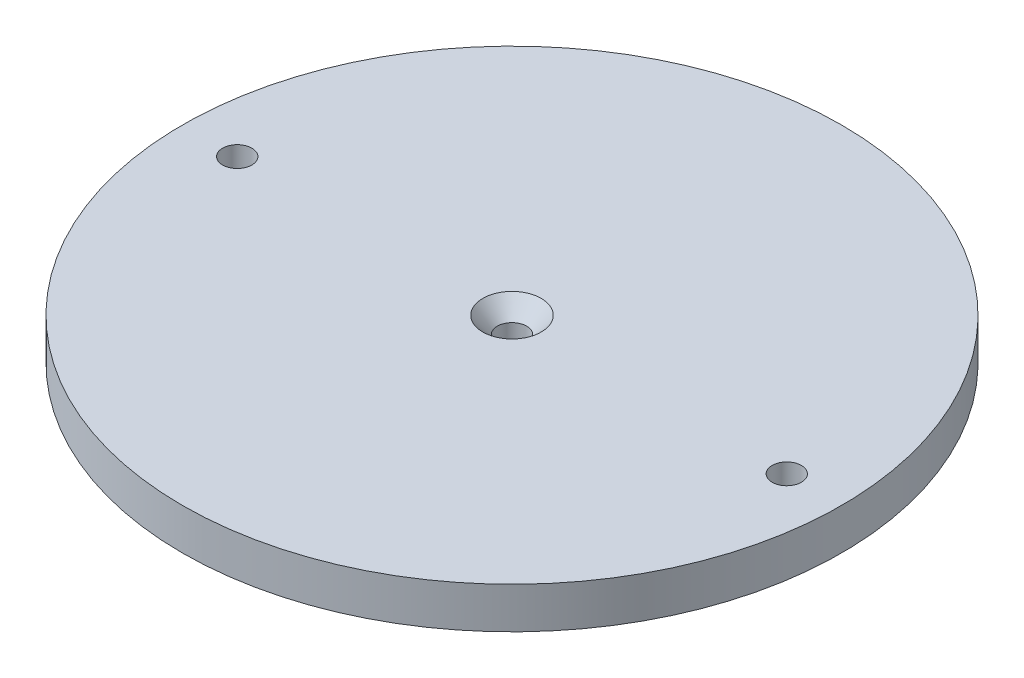
SolidWorks part; units mm, degrees
material "6061 Alloy"
ref_plane "Front Plane" through (0, 0, 0) normal (0, 0, 1) x (1, 0, 0)
ref_plane "Top Plane" through (0, 0, 0) normal (0, 1, 0) x (1, 0, 0)
ref_plane "Right Plane" through (0, 0, 0) normal (1, 0, 0) x (0, 0, -1)
sketch "Sketch2" plane through (0, 0, 0) normal (0, 1, 0) x (1, 0, 0)
  circle A0 centre (0, 0) radius 76.1619
  dimension "D1" = 152.3238
extrude "Boss-Extrude1" add sketch "Sketch2" along normal blind 9.525
sketch "Sketch3" plane through (0, 9.525, 0) normal (0, 1, 0) x (1, 0, 0)
  point P0 (-63.5, 0)
  point P1 (63.5, 0)
  point P2 (-63.2099, 6.0633)
  point P4 (0, 0)
  dimension "D1" = 63.5
  dimension "D2" = 63.5
hole_wizard "1/4 Clearance Hole1" positions "Sketch3" profile "Sketch4" hole size "1/4" standard "ANSI Inch" end condition through all
sketch "Sketch4" plane through (-63.5, 9.525, 0) normal (1, 0, 0) x (0, 0, 1)
  line L0 (0, 0) -> (0, 9.525)
  line L1 (0, 9.525) -> (3.3782, 9.525)
  line L2 (3.3782, 9.525) -> (3.3782, 0)
  line L5 (3.3782, 0) -> (0, 0)
  line L11 (0, -6.35) -> (0, 107.95) construction
  dimension "Thru Hole Dia." = 6.7564
  dimension "Thru Hole Depth" = 9.525
sketch "Sketch5" plane through (0, 9.525, 0) normal (0, 1, 0) x (1, 0, 0)
  point P0 (0, 0)
hole_wizard "CSK for 1/4 Flat Head Machine Screw1" positions "Sketch5" profile "Sketch7" countersink size "1/4" standard "ANSI Inch" end condition through all
sketch "Sketch7" plane through (0, 9.525, 0) normal (1, 0, 0) x (0, 0, 1)
  line L0 (0, 0) -> (0, 9.525)
  line L1 (0, 9.525) -> (3.3782, 9.525)
  line L2 (3.3782, 9.525) -> (3.3782, 3.8716)
  line L3 (3.3782, 3.8716) -> (6.7437, 0)
  line L5 (6.7437, 0) -> (0, 0)
  line L6 (-3.3782, 3.8716) -> (-6.7437, 0) construction
  line L11 (0, -6.35) -> (0, 107.95) construction
  dimension "Thru Hole Dia." = 6.7564
  dimension "Thru Hole Depth" = 9.525
  dimension "Near C'Sink Dia." = 13.4874
  dimension "Near C'Sink Angle" = 82
equation "\"outerdiameter\"= 5.997"
equation "\"platethickness\"= 0.375"
equation "\"holespacing\"= 2.5"
equation "\"D1@Sketch2\"=\"outerdiameter\""
equation "\"D1@Boss-Extrude1\"=\"platethickness\""
equation "\"D2@Sketch3\"=\"holespacing\""
equation "\"D1@Sketch3\"=\"holespacing\""
